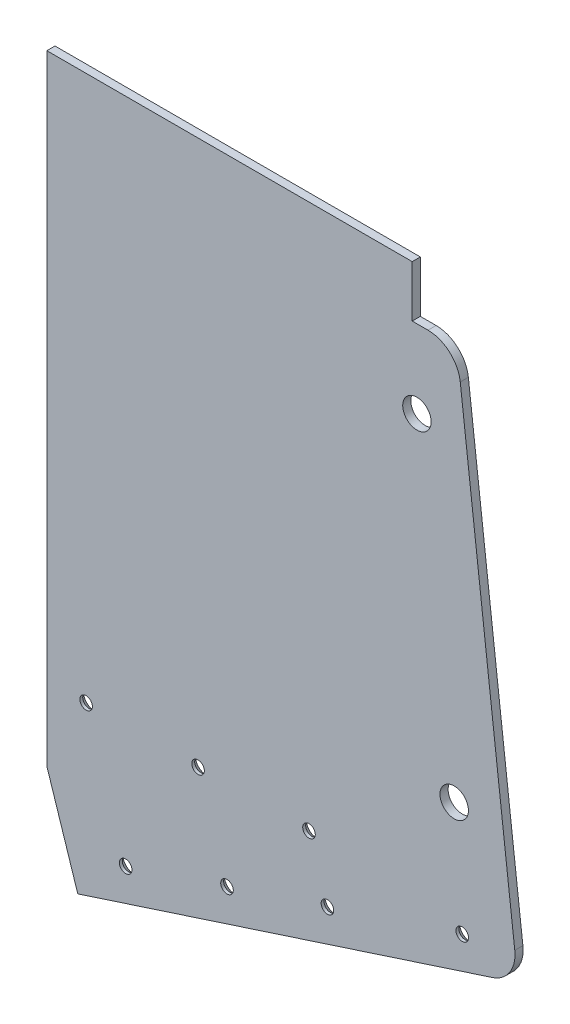
SolidWorks part; units mm, degrees
material "Acrylic (Medium-high impact)"
ref_plane "Front Plane" through (0, 0, 0) normal (0, 0, 1) x (1, 0, 0)
ref_plane "Top Plane" through (0, 0, 0) normal (0, 1, 0) x (1, 0, 0)
ref_plane "Right Plane" through (0, 0, 0) normal (1, 0, 0) x (0, 0, -1)
sketch "Sketch1" plane through (0, 0, 0) normal (0, 0, 1) x (1, 0, 0)
  line L1 (-234.753, 12.7) -> (-91.9973, 12.7)
  line L2 (-234.753, 12.7) -> (-234.753, -270.5428)
  line L3 (-234.753, -270.5428) -> (-50.7003, -210.6746)
  line L4 (-74.5335, -7.417) -> (-50.7003, -210.6746)
  line L5 (-64.9774, -197.966) -> (-88.1902, 0) construction
  line L8 (-74.5335, -7.417) -> (-91.9973, -7.417)
  line L9 (-91.9973, -7.417) -> (-91.9973, 12.7)
  line L10 (-91.9973, 0) -> (-91.9973, 12.7) construction
  dimension "D1" = 12.7
  dimension "D2" = 71.981
  dimension "D3" = 283.2428
extrude "Boss-Extrude1" add sketch "Sketch1" along normal blind 3.175
fillet "Fillet1" radius 12.7 2 edges at (-74.5335, -7.417, 1.5875) (-50.7003, -210.6746, 1.5875)
sketch "Sketch2" plane through (0, 0, 3.175) normal (0, 0, 1) x (1, 0, 0)
  line L0 (-234.753, -270.5428) -> (-60.5975, -213.8939) construction
  line L1 (-234.753, 12.7) -> (-234.753, -270.5428) construction
  line L2 (-234.753, -270.5428) -> (-222.6758, -266.6143)
  line L3 (-234.753, -229.4856) -> (-234.753, -270.5428)
  line L4 (-222.6758, -266.6143) -> (-234.753, -229.4856)
  dimension "D1" = 12.7
extrude "Cut-Extrude1" cut sketch "Sketch2" against normal through all
hole_wizard "CSK for #8 Flat Head Machine Screw1" positions "Sketch3" profile "Sketch4" countersink size "#8" standard "ANSI Inch" end condition through all
sketch "Sketch3" plane through (0, 0, 0) normal (0, 0, -1) x (-1, 0, 0)
  point P0 (203.9698, -247.917)
  point P3 (164.3688, -235.0357)
  point P6 (175.687, -200.2402)
  point P9 (219.4388, -200.3608)
  point P12 (125.1181, -222.2683)
  point P15 (132.3222, -200.1207)
  point P18 (72.4521, -205.1373)
sketch "Sketch4" plane through (-203.9698, -247.917, 0) normal (1, 0, 0) x (0, 1, 0)
  line L0 (0, 0) -> (0, 3.175)
  line L1 (0, 3.175) -> (2.4574, 3.175)
  line L2 (2.4574, 3.175) -> (2.4574, 2.0234)
  line L3 (2.4574, 2.0234) -> (4.2164, 0)
  line L5 (4.2164, 0) -> (0, 0)
  line L6 (-2.4574, 2.0234) -> (-4.2164, 0) construction
  line L11 (0, -6.35) -> (0, 107.95) construction
  dimension "Thru Hole Dia." = 4.9149
  dimension "Thru Hole Depth" = 3.175
  dimension "Near C'Sink Dia." = 8.4328
  dimension "Near C'Sink Angle" = 82
sketch "Sketch5" plane through (0, 0, 3.175) normal (0, 0, 1) x (1, 0, 0)
  circle A0 centre (-90.1466, -37.8408) radius 5.5563
  circle A1 centre (-75.5767, -162.098) radius 5.5563
  dimension "D1" = 11.1125
extrude "Cut-Extrude2" cut sketch "Sketch5" against normal up to next
